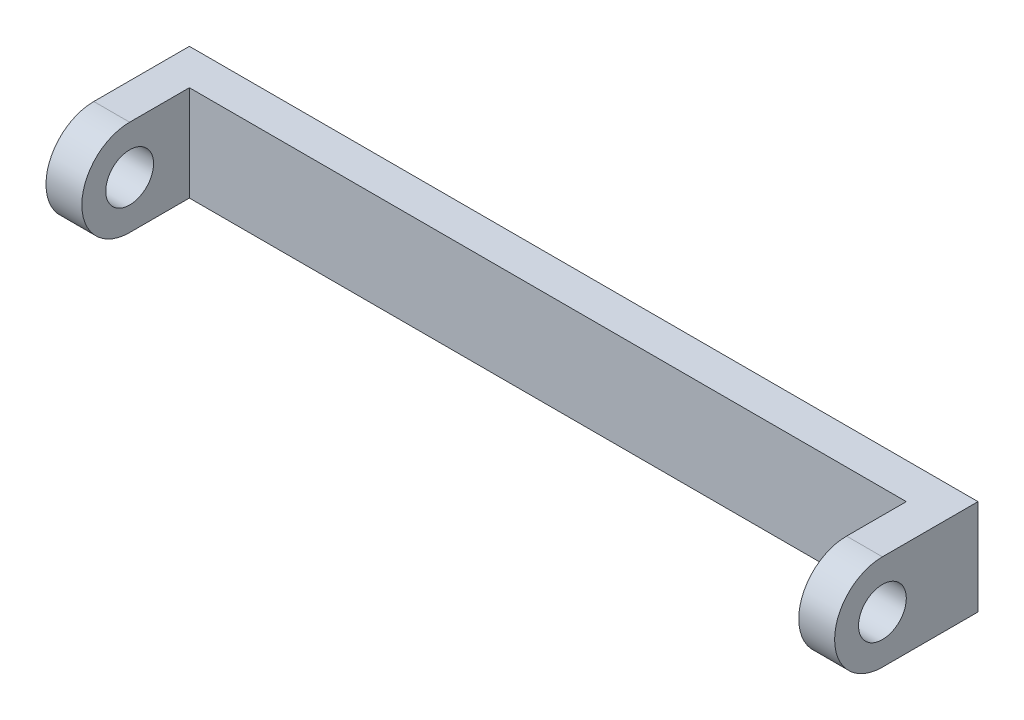
SolidWorks part; units mm, degrees
ref_plane "Front Plane" through (0, 0, 0) normal (0, 0, 1) x (1, 0, 0)
ref_plane "Top Plane" through (0, 0, 0) normal (0, 1, 0) x (1, 0, 0)
ref_plane "Right Plane" through (0, 0, 0) normal (1, 0, 0) x (0, 0, -1)
sketch "Sketch1" plane through (0, 0, 0) normal (0, 0, 1) x (1, 0, 0)
  line L0 (-34.3957, -2.6644) -> (-34.3957, 5.3356)
  line L1 (-37.3957, 5.3356) -> (-4.3957, 5.3356)
  line L2 (-37.3957, 5.3356) -> (-37.3957, -2.6644)
  line L3 (-37.3957, -2.6644) -> (-4.3957, -2.6644)
  line L4 (-4.3957, 5.3356) -> (-4.3957, -2.6644)
  dimension "D1" = 33
  dimension "D2" = 8
  dimension "D3" = 3
extrude "Boss-Extrude3" add sketch "Sketch1" along normal blind 3 contours L2 L3 L0 L1 | L4 L1 L0 L3 region at (-35.8957, 1.3356, 0) region at (-19.3957, 1.3356, 0)
sketch "Sketch6" plane through (0, 0, 3) normal (0, 0, 1) x (1, 0, 0)
  line L0 (-34.3957, 5.3356) -> (-34.3957, -2.6644)
  line L1 (-37.3957, 5.3356) -> (-4.3957, 5.3356) construction
  line L2 (-37.3957, -2.6644) -> (-4.3957, -2.6644) construction
  line L3 (-37.3957, 5.3356) -> (-37.3957, -2.6644) construction
  line L8 (-37.3957, 5.3356) -> (-37.3957, -2.6644)
  line L9 (-37.3957, -2.6644) -> (-4.3957, -2.6644)
  line L10 (-4.3957, -2.6644) -> (-4.3957, 5.3356)
  line L11 (-4.3957, 5.3356) -> (-37.3957, 5.3356)
  line L12 (-37.3957, 5.3356) -> (-37.3957, -2.6644)
  line L13 (-37.3957, -2.6644) -> (-34.3957, -2.6644)
  line L15 (-34.3957, 5.3356) -> (-37.3957, 5.3356)
  dimension "D1" = 3
  dimension "D2" = 0
extrude "Boss-Extrude5" add sketch "Sketch6" along normal blind 9
fillet "Fillet3" 2 edges at (-35.8957, -2.6644, 12) (-35.8957, 5.3356, 12) type full round first side face at (-25.3957, -2.6644, 5) second side face at (-25.3957, 5.3356, 5) middle face at (-35.8957, 1.3356, 12)
sketch "Sketch7" plane through (-34.3957, 0, 0) normal (1, 0, 0) x (0, 0, -1)
  circle A0 centre (-8, 1.3356) radius 2
  dimension "D1" = 4
extrude "Cut-Extrude1" cut sketch "Sketch7" against normal through all
ref_plane "Plane1" through (-4.3957, 0, 0) normal (1, 0, 0) x (0, 0, -1)
mirror "Mirror1" about plane through (-4.3957, 0, 0) normal (1, 0, 0) of "Fillet3", "Cut-Extrude1", "Boss-Extrude5", "Boss-Extrude3"
